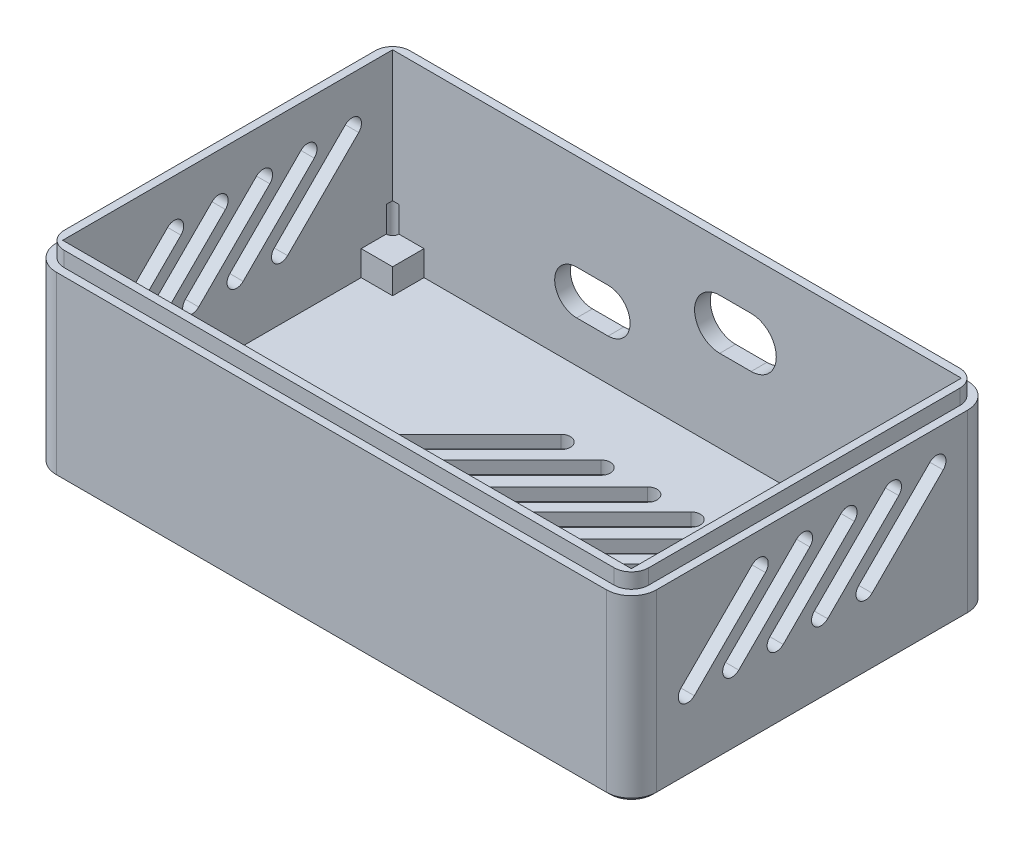
SolidWorks part; units mm, degrees
ref_plane "Front Plane" through (0, 0, 0) normal (0, 0, 1) x (1, 0, 0)
ref_plane "Top Plane" through (0, 0, 0) normal (0, 1, 0) x (1, 0, 0)
ref_plane "Right Plane" through (0, 0, 0) normal (1, 0, 0) x (0, 0, -1)
sketch "Croquis_contorno" plane through (0, 0, 0) normal (0, 1, 0) x (1, 0, 0)
  line L0 (-43.75, -28.75) -> (43.75, -28.75)
  line L1 (47.75, -24.75) -> (47.75, 24.75)
  line L2 (43.75, 28.75) -> (-43.75, 28.75)
  line L3 (-47.75, 24.75) -> (-47.75, -24.75)
  arc A0 (43.75, -28.75) -> (47.75, -24.75) centre (43.75, -24.75) ccw
  arc A1 (47.75, 24.75) -> (43.75, 28.75) centre (43.75, 24.75) ccw
  arc A2 (-43.75, 28.75) -> (-47.75, 24.75) centre (-43.75, 24.75) ccw
  arc A3 (-47.75, -24.75) -> (-43.75, -28.75) centre (-43.75, -24.75) ccw
  dimension "D3" = 4
  dimension "D1" = 95.5
  dimension "D2" = 57.5
extrude "Cuerpo" add sketch "Croquis_contorno" along normal blind 28.5
ref_plane "Plano_Top Plane_+28_5" through (0, 28.5, 0) normal (0, 1, 0) x (1, 0, 0)
sketch "Croquis_hueco_PCB" plane through (0, 28.5, 0) normal (0, 1, 0) x (1, 0, 0)
  line L1 (-45.25, -26.25) -> (45.25, -26.25)
  line L2 (-45.25, -26.25) -> (-45.25, 26.25)
  line L3 (-45.25, 26.25) -> (45.25, 26.25)
  line L4 (45.25, -26.25) -> (45.25, 26.25)
  line L5 (-45.25, -26.25) -> (45.25, 26.25) construction
  line L6 (-45.25, 26.25) -> (45.25, -26.25) construction
  dimension "D1" = 90.5
  dimension "D2" = 52.5
extrude "Hueco_PCB" cut sketch "Croquis_hueco_PCB" against normal blind 26.5
sketch "Croquis_labio" plane through (0, 28.5, 0) normal (0, 1, 0) x (1, 0, 0)
  line L0 (-43.75, -27.5) -> (43.75, -27.5)
  line L1 (46.5, -24.75) -> (46.5, 24.75)
  line L2 (43.75, 27.5) -> (-43.75, 27.5)
  line L3 (-46.5, 24.75) -> (-46.5, -24.75)
  line L5 (-45.25, -26.25) -> (45.25, -26.25)
  line L6 (-45.25, -26.25) -> (-45.25, 26.25)
  line L7 (-45.25, 26.25) -> (45.25, 26.25)
  line L8 (45.25, -26.25) -> (45.25, 26.25)
  line L9 (-45.25, -26.25) -> (45.25, 26.25) construction
  line L10 (-45.25, 26.25) -> (45.25, -26.25) construction
  arc A0 (43.75, -27.5) -> (46.5, -24.75) centre (43.75, -24.75) ccw
  arc A1 (46.5, 24.75) -> (43.75, 27.5) centre (43.75, 24.75) ccw
  arc A2 (-43.75, 27.5) -> (-46.5, 24.75) centre (-43.75, 24.75) ccw
  arc A3 (-46.5, -24.75) -> (-43.75, -27.5) centre (-43.75, -24.75) ccw
  point P12 (0, 0)
  dimension "D3" = 2.75
  dimension "D1" = 93
  dimension "D2" = 55
extrude "Labio_lip" add sketch "Croquis_labio" along normal blind 2.4
ref_plane "Plano_Top Plane_+2" through (0, 2, 0) normal (0, 1, 0) x (1, 0, 0)
sketch "Croquis_apoyos" plane through (0, 2, 0) normal (0, 1, 0) x (1, 0, 0)
  line L0 (45.25, 26.25) -> (-45.25, 26.25) construction
  line L1 (-45.25, -26.25) -> (-40.25, -26.25)
  line L2 (-45.25, -26.25) -> (-45.25, -21.25)
  line L3 (-45.25, -21.25) -> (-40.25, -21.25)
  line L4 (-40.25, -26.25) -> (-40.25, -21.25)
  line L5 (-45.25, -26.25) -> (-40.25, -21.25) construction
  line L6 (-45.25, -21.25) -> (-40.25, -26.25) construction
  line L7 (-45.25, 21.25) -> (-40.25, 21.25)
  line L8 (-45.25, 21.25) -> (-45.25, 26.25)
  line L9 (-45.25, 26.25) -> (-40.25, 26.25)
  line L10 (-40.25, 21.25) -> (-40.25, 26.25)
  line L11 (-45.25, 21.25) -> (-40.25, 26.25) construction
  line L12 (-45.25, 26.25) -> (-40.25, 21.25) construction
  line L13 (45.25, -26.25) -> (45.25, 26.25) construction
  line L14 (40.25, -26.25) -> (45.25, -26.25)
  line L15 (40.25, -26.25) -> (40.25, -21.25)
  line L16 (40.25, -21.25) -> (45.25, -21.25)
  line L17 (45.25, -26.25) -> (45.25, -21.25)
  line L18 (40.25, -26.25) -> (45.25, -21.25) construction
  line L19 (40.25, -21.25) -> (45.25, -26.25) construction
  line L21 (40.25, 21.25) -> (45.25, 21.25)
  line L22 (40.25, 21.25) -> (40.25, 26.25)
  line L23 (40.25, 26.25) -> (45.25, 26.25)
  line L24 (45.25, 21.25) -> (45.25, 26.25)
  line L25 (40.25, 21.25) -> (45.25, 26.25) construction
  line L26 (40.25, 26.25) -> (45.25, 21.25) construction
  point P0 (-42.75, 23.75)
  point P11 (42.75, -23.75)
  point P18 (42.75, 23.75)
  dimension "D1" = 5
  dimension "D2" = 5
extrude "Apoyos_PCB" add sketch "Croquis_apoyos" along normal blind 4
sketch "Croquis_alivios" plane through (0, 2, 0) normal (0, 1, 0) x (1, 0, 0)
  circle A0 centre (-45.25, -26.25) radius 1
  circle A1 centre (-45.25, 26.25) radius 1
  circle A2 centre (45.25, -26.25) radius 1
  circle A3 centre (45.25, 26.25) radius 1
  dimension "D1" = 2
extrude "Alivios_esquinas" cut sketch "Croquis_alivios" along normal blind 8.1
sketch "Croquis_salidas" plane through (0, 0, 0) normal (0, 0, 1) x (1, 0, 0)
  line L0 (6.8, 19.1) -> (11.8, 19.1) construction
  line L1 (6.8, 23.1) -> (11.8, 23.1)
  line L2 (6.8, 15.1) -> (11.8, 15.1)
  line L3 (-15.96, 12.1) -> (-10.96, 12.1) construction
  line L4 (-15.96, 15.6) -> (-10.96, 15.6)
  line L5 (-15.96, 8.6) -> (-10.96, 8.6)
  arc A0 (6.8, 23.1) -> (6.8, 15.1) centre (6.8, 19.1) ccw
  arc A1 (11.8, 15.1) -> (11.8, 23.1) centre (11.8, 19.1) ccw
  arc A2 (-15.96, 15.6) -> (-15.96, 8.6) centre (-15.96, 12.1) ccw
  arc A3 (-10.96, 8.6) -> (-10.96, 15.6) centre (-10.96, 12.1) ccw
  point P2 (9.3, 19.1)
  point P7 (-13.46, 12.1)
  point P14 (0, 0)
extrude "Salidas_USB_y_panel" cut sketch "Croquis_salidas" against normal through all
sketch "Croquis_ventilas" plane through (0, 0, 0) normal (1, 0, 0) x (0, 0, -1)
  line L0 (-19.799, 11.9431) -> (-8.4853, 23.2569) construction
  line L1 (-20.8597, 13.0038) -> (-9.5459, 24.3175)
  line L2 (-18.7383, 10.8825) -> (-7.4246, 22.1962)
  line L3 (-12.7279, 11.9431) -> (-1.4142, 23.2569) construction
  line L4 (-13.7886, 13.0038) -> (-2.4749, 24.3175)
  line L5 (-11.6673, 10.8825) -> (-0.3536, 22.1962)
  line L6 (-5.6569, 11.9431) -> (5.6569, 23.2569) construction
  line L7 (-6.7175, 13.0038) -> (4.5962, 24.3175)
  line L8 (-4.5962, 10.8825) -> (6.7175, 22.1962)
  line L9 (1.4142, 11.9431) -> (12.7279, 23.2569) construction
  line L10 (0.3536, 13.0038) -> (11.6673, 24.3175)
  line L11 (2.4749, 10.8825) -> (13.7886, 22.1962)
  line L12 (8.4853, 11.9431) -> (19.799, 23.2569) construction
  line L13 (7.4246, 13.0038) -> (18.7383, 24.3175)
  line L14 (9.5459, 10.8825) -> (20.8597, 22.1962)
  arc A0 (-20.8597, 13.0038) -> (-18.7383, 10.8825) centre (-19.799, 11.9431) ccw
  arc A1 (-7.4246, 22.1962) -> (-9.5459, 24.3175) centre (-8.4853, 23.2569) ccw
  arc A2 (-13.7886, 13.0038) -> (-11.6673, 10.8825) centre (-12.7279, 11.9431) ccw
  arc A3 (-0.3536, 22.1962) -> (-2.4749, 24.3175) centre (-1.4142, 23.2569) ccw
  arc A4 (-6.7175, 13.0038) -> (-4.5962, 10.8825) centre (-5.6569, 11.9431) ccw
  arc A5 (6.7175, 22.1962) -> (4.5962, 24.3175) centre (5.6569, 23.2569) ccw
  arc A6 (0.3536, 13.0038) -> (2.4749, 10.8825) centre (1.4142, 11.9431) ccw
  arc A7 (13.7886, 22.1962) -> (11.6673, 24.3175) centre (12.7279, 23.2569) ccw
  arc A8 (7.4246, 13.0038) -> (9.5459, 10.8825) centre (8.4853, 11.9431) ccw
  arc A9 (20.8597, 22.1962) -> (18.7383, 24.3175) centre (19.799, 23.2569) ccw
  point P2 (-14.1421, 17.6)
  point P7 (-7.0711, 17.6)
  point P14 (0, 17.6)
  point P21 (7.0711, 17.6)
  point P28 (14.1421, 17.6)
  point P35 (0, 0)
extrude "Ventilas_laterales" cut sketch "Croquis_ventilas" along normal through all and the other way through all
sketch "Croquis_rejilla_piso" plane through (0, 0, 0) normal (0, 1, 0) x (1, 0, 0)
  line L0 (-35.7089, -14.4957) -> (-6.7175, 14.4957) construction
  line L1 (-36.7696, -13.435) -> (-7.7782, 15.5563)
  line L2 (-34.6482, -15.5563) -> (-5.6569, 13.435)
  line L3 (-28.6378, -14.4957) -> (0, 14.1421) construction
  line L4 (-29.6985, -13.435) -> (-1.0607, 15.2028)
  line L5 (-27.5772, -15.5563) -> (1.0607, 13.0815)
  line L6 (-21.2132, -14.4957) -> (7.4246, 14.1421) construction
  line L7 (-22.2739, -13.435) -> (6.364, 15.2028)
  line L8 (-20.1525, -15.5563) -> (8.4853, 13.0815)
  line L9 (-14.3189, -14.4957) -> (14.3189, 14.1421) construction
  line L10 (-15.3796, -13.435) -> (13.2583, 15.2028)
  line L11 (-13.2583, -15.5563) -> (15.3796, 13.0815)
  line L12 (-6.8943, -14.4957) -> (21.7435, 14.1421) construction
  line L13 (-7.955, -13.435) -> (20.6829, 15.2028)
  line L14 (-5.8336, -15.5563) -> (22.8042, 13.0815)
  line L15 (0, -14.4957) -> (28.6378, 14.1421) construction
  line L16 (-1.0607, -13.435) -> (27.5772, 15.2028)
  line L17 (1.0607, -15.5563) -> (29.6985, 13.0815)
  line L18 (6.364, -14.4957) -> (35.5321, 14.6725) construction
  line L19 (5.3033, -13.435) -> (34.4715, 15.7331)
  line L20 (7.4246, -15.5563) -> (36.5928, 13.6118)
  arc A0 (-36.7696, -13.435) -> (-34.6482, -15.5563) centre (-35.7089, -14.4957) ccw
  arc A1 (-5.6569, 13.435) -> (-7.7782, 15.5563) centre (-6.7175, 14.4957) ccw
  arc A2 (-29.6985, -13.435) -> (-27.5772, -15.5563) centre (-28.6378, -14.4957) ccw
  arc A3 (1.0607, 13.0815) -> (-1.0607, 15.2028) centre (0, 14.1421) ccw
  arc A4 (-22.2739, -13.435) -> (-20.1525, -15.5563) centre (-21.2132, -14.4957) ccw
  arc A5 (8.4853, 13.0815) -> (6.364, 15.2028) centre (7.4246, 14.1421) ccw
  arc A6 (-15.3796, -13.435) -> (-13.2583, -15.5563) centre (-14.3189, -14.4957) ccw
  arc A7 (15.3796, 13.0815) -> (13.2583, 15.2028) centre (14.3189, 14.1421) ccw
  arc A8 (-7.955, -13.435) -> (-5.8336, -15.5563) centre (-6.8943, -14.4957) ccw
  arc A9 (22.8042, 13.0815) -> (20.6829, 15.2028) centre (21.7435, 14.1421) ccw
  arc A10 (-1.0607, -13.435) -> (1.0607, -15.5563) centre (0, -14.4957) ccw
  arc A11 (29.6985, 13.0815) -> (27.5772, 15.2028) centre (28.6378, 14.1421) ccw
  arc A12 (5.3033, -13.435) -> (7.4246, -15.5563) centre (6.364, -14.4957) ccw
  arc A13 (36.5928, 13.6118) -> (34.4715, 15.7331) centre (35.5321, 14.6725) ccw
  point P2 (-21.2132, 0)
  point P7 (-14.3189, -0.1768)
  point P14 (-6.8943, -0.1768)
  point P21 (0, -0.1768)
  point P28 (7.4246, -0.1768)
  point P35 (14.3189, -0.1768)
  point P42 (20.948, 0.0884)
  point P49 (0, 0)
extrude "Rejilla_piso" cut sketch "Croquis_rejilla_piso" along normal blind 2
chamfer "Chaflan_base" distance 0.6 angle 45 8 edges at (0, 0, 28.75) (46.5784, 0, 27.5784) (47.75, 0, 0) (46.5784, 0, -27.5784) (0, 0, -28.75) (-46.5784, 0, -27.5784) (-47.75, 0, 0) (-46.5784, 0, 27.5784) tangent propagation no
